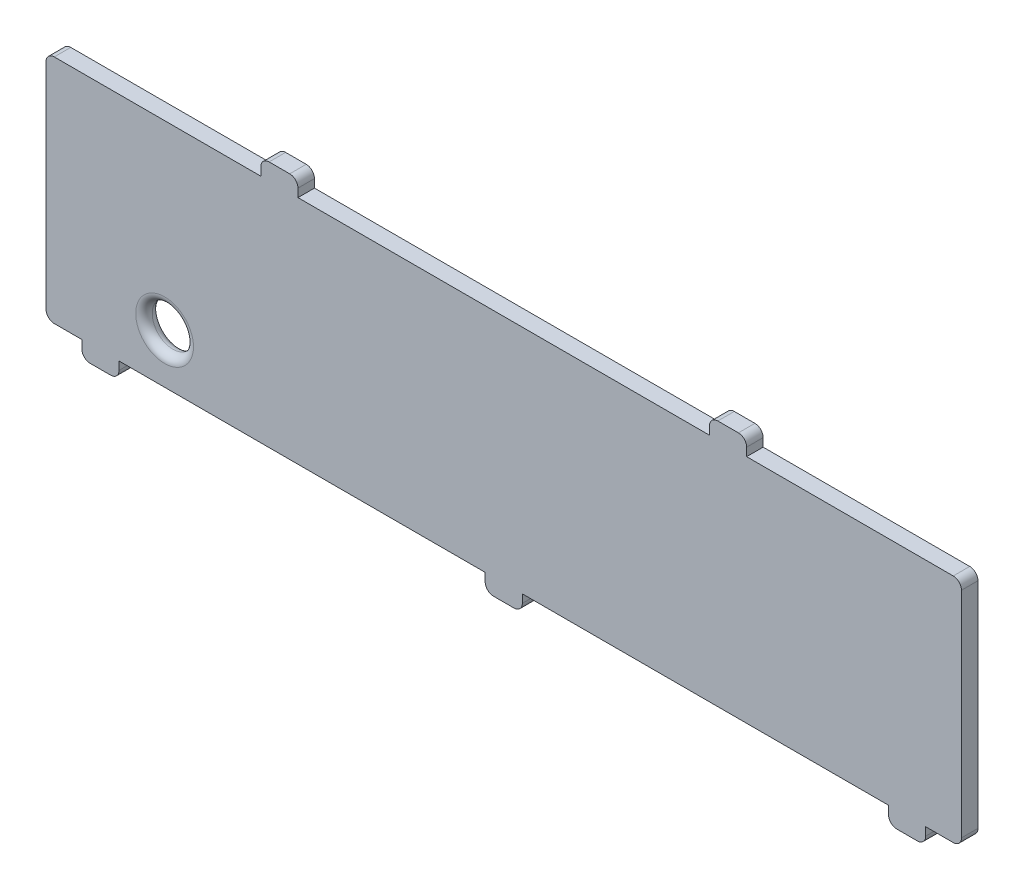
SolidWorks part; units mm, degrees
ref_plane "前基準面" through (0, 0, 0) normal (0, 0, 1) x (1, 0, 0)
ref_plane "上基準面" through (0, 0, 0) normal (0, 1, 0) x (1, 0, 0)
ref_plane "右基準面" through (0, 0, 0) normal (1, 0, 0) x (0, 0, -1)
sketch "Sketch1" plane through (0, 0, 0) normal (0, 0, 1) x (1, 0, 0)
  line L0 (0, 0) -> (0, -31.2064) construction
  line L1 (-55.5, 14) -> (55.5, 14)
  line L2 (-55.5, 14) -> (-55.5, -14)
  line L3 (-55.5, -14) -> (55.5, -14)
  line L4 (55.5, 14) -> (55.5, -14)
  line L5 (-55.5, 14) -> (55.5, -14) construction
  line L6 (-55.5, -14) -> (55.5, 14) construction
  line L7 (0, -31.2064) -> (0, 29.4941) construction
  line L8 (-2.25, -14) -> (2.25, -16) construction
  line L9 (-2.25, -14) -> (2.25, -14)
  line L10 (-2.25, -14) -> (-2.25, -16)
  line L11 (-2.25, -16) -> (2.25, -16)
  line L12 (2.25, -14) -> (2.25, -16)
  line L13 (-2.25, -16) -> (2.25, -14) construction
  line L14 (-51.15, -14) -> (-46.65, -16) construction
  line L15 (-51.15, -14) -> (-46.65, -14)
  line L16 (-51.15, -14) -> (-51.15, -16)
  line L17 (-51.15, -16) -> (-46.65, -16)
  line L18 (-46.65, -14) -> (-46.65, -16)
  line L19 (-46.65, -14) -> (-51.15, -16) construction
  line L20 (51.15, -16) -> (46.65, -16)
  line L21 (46.65, -14) -> (46.65, -16)
  line L22 (51.15, -14) -> (46.65, -14)
  line L23 (51.15, -14) -> (51.15, -16)
  line L24 (-48.9, -15) -> (-48.9, 18.4346) construction
  line L25 (0, -15.6032) -> (0, 17.9346) construction
  line L26 (46.65, -14) -> (51.15, -16) construction
  line L27 (51.15, -14) -> (46.65, -16) construction
  line L28 (-29.45, 16) -> (-24.95, 14) construction
  line L29 (-29.45, 14) -> (-24.95, 14)
  line L30 (-29.45, 14) -> (-29.45, 16)
  line L31 (-29.45, 16) -> (-24.95, 16)
  line L32 (-24.95, 14) -> (-24.95, 16)
  line L33 (-24.95, 16) -> (-29.45, 14) construction
  line L34 (29.45, 16) -> (24.95, 16)
  line L35 (24.95, 14) -> (24.95, 16)
  line L36 (29.45, 14) -> (24.95, 14)
  line L37 (29.45, 14) -> (29.45, 16)
  point P0 (0, 0)
  point P13 (0, -15)
  point P32 (-27.2, 15)
  dimension "D1" = 28
  dimension "D2" = 111
  dimension "D3" = 2
  dimension "D4" = 4.5
  dimension "D5" = 2
  dimension "D6" = 4.5
  dimension "D7" = 6.6
  dimension "D8" = 2
  dimension "D9" = 4.5
  dimension "D10" = 27.2
extrude "Boss-Extrude1" add sketch "Sketch1" along normal mid plane 2 contours L4 L1 L2 L3 | L12 L3 L10 L11 | L1 L37 L34 L35 | L1 L32 L31 L30 | L18 L17 L16 L15 | L23 L20 L21 L22 region at (0, 0, 0) region at (-27.2, 15, 0) region at (27.2, 15, 0) region at (0, -15, 0)
fillet "Fillet1" radius 1 14 edges at (-55.5, 14, 0) (-55.5, -14, 0) (-46.65, -16, 0) (-51.15, -16, 0) (2.25, -16, 0) (-2.25, -16, 0) (46.65, -16, 0) (51.15, -16, 0) (55.5, -14, 0) (55.5, 14, 0) (29.45, 16, 0) (24.95, 16, 0) (-24.95, 16, 0) (-29.45, 16, 0)
sketch "Sketch3" plane through (0, 0, 1) normal (0, 0, 1) x (1, 0, 0)
  line L0 (-41.12, -0.6049) -> (-41.12, -16) construction
  line L1 (-60.75, -16) -> (60.25, -16) construction
  line L2 (-56, 13) -> (-56, -13) construction
  circle A0 centre (-41.12, -8) radius 2.5
  dimension "D1" = 5
  dimension "D2" = 8
  dimension "D3" = 14.88
extrude "Cut-Extrude1" cut sketch "Sketch3" against normal up to next
fillet "Fillet2" radius 1 2 edges at (-38.62, -8, -1) (-38.62, -8, 1)
